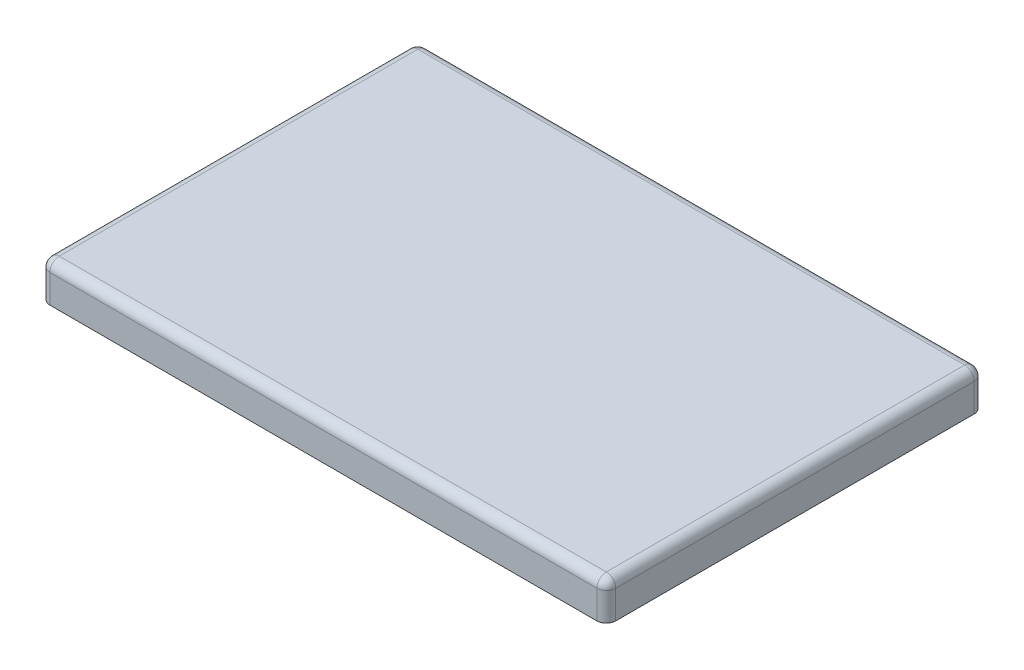
SolidWorks part; units mm, degrees
material "Acrylic (Medium-high impact)"
ref_plane "Front Plane" through (0, 0, 0) normal (0, 0, 1) x (1, 0, 0)
ref_plane "Top Plane" through (0, 0, 0) normal (0, 1, 0) x (1, 0, 0)
ref_plane "Right Plane" through (0, 0, 0) normal (1, 0, 0) x (0, 0, -1)
sketch "Sketch1" plane through (0, 0, 0) normal (0, 1, 0) x (1, 0, 0)
  line L1 (-72.5, -50) -> (72.5, -50)
  line L2 (-75, -47.5) -> (-75, 47.5)
  line L3 (-72.5, 50) -> (72.5, 50)
  line L4 (75, -47.5) -> (75, 47.5)
  line L5 (-75, -50) -> (75, 50) construction
  line L6 (-75, 50) -> (75, -50) construction
  arc A0 (-72.5, -50) -> (-75, -47.5) centre (-72.5, -47.5) cw
  arc A1 (72.5, -50) -> (75, -47.5) centre (72.5, -47.5) ccw
  arc A2 (72.5, 50) -> (75, 47.5) centre (72.5, 47.5) cw
  arc A3 (-75, 47.5) -> (-72.5, 50) centre (-72.5, 47.5) cw
  point P0 (0, 0)
  dimension "D3" = 2.5
  dimension "D1" = 150
  dimension "D2" = 100
extrude "Boss-Extrude1" add sketch "Sketch1" along normal blind 10
shell "Shell1" thickness 1.25 removed face at (0, 0, 0)
fillet "Fillet1" radius 2.5 8 edges at (-75, 10, 0) (-74.2678, 10, -49.2678) (0, 10, -50) (74.2678, 10, -49.2678) (75, 10, 0) (74.2678, 10, 49.2678) (0, 10, 50) (-74.2678, 10, 49.2678)
chamfer "Chamfer1" distance 1.25 angle 45 8 edges at (-73.75, 0, 0) (-73.3839, 0, -48.3839) (-73.3839, 0, 48.3839) (0, 0, -48.75) (0, 0, 48.75) (73.3839, 0, -48.3839) (73.75, 0, 0) (73.3839, 0, 48.3839)
